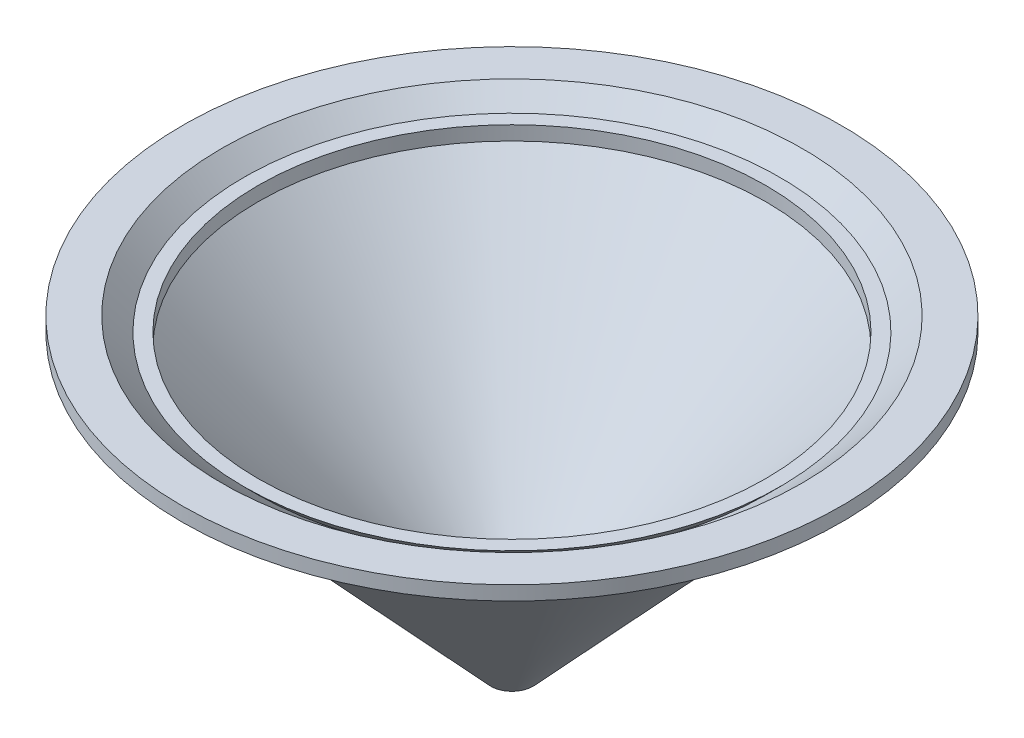
SolidWorks part; units mm, degrees
other "Markup1"
sketch "Sketch4" plane through (66.75, 2, 66.75) normal (0.1882, 0.8238, 0.5348) x (0.9745, -0.0887, -0.2062)
other "Markup2"
sketch "Sketch5" plane through (-66.75, 2, 66.75) normal (-0.3605, 0.8664, 0.3456) x (0.6787, -0.0106, 0.7344)
ref_plane "Front Plane" through (0, 0, 0) normal (0, 0, 1) x (1, 0, 0)
ref_plane "Top Plane" through (0, 0, 0) normal (0, 1, 0) x (1, 0, 0)
ref_plane "Right Plane" through (0, 0, 0) normal (1, 0, 0) x (0, 0, -1)
sketch "Sketch1" plane through (0, 0, 0) normal (0, 1, 0) x (1, 0, 0)
  circle A0 centre (0, 0) radius 46.7275
  dimension "D1" = 93.455
sketch "Sketch2" plane through (0, 0, 0) normal (0, 0, 1) x (1, 0, 0)
  line L0 (0, 0) -> (0, -42)
  line L1 (-42, 0) -> (-3, -42)
  line L2 (46.7275, 0) -> (-46.7275, 0) construction
  line L3 (0, -42) -> (-3, -42)
  line L4 (0, 0) -> (-42, 0)
  line L5 (-3, -42) -> (0, -45) construction
  line L6 (0, -45) -> (0, -42) construction
  dimension "D1" = 42
  dimension "D2" = 42
  dimension "D3" = 3
  dimension "D4" = 3
revolve "Revolve1" add sketch "Sketch2" angle 360 about L0
extrude "Boss-Extrude2" add sketch "Sketch1" along normal blind 2 contours A0
shell "Shell1" thickness 2 removed face at (-3, -42, 0) removed face at (0, 2, 46.7275)
sketch "Sketch3" plane through (0, 0, 0) normal (1, 0, 0) x (0, 0, -1)
  line L0 (-38, 0) -> (-36, 0)
  line L1 (-46.7275, 0) -> (46.7275, 0) construction
  line L2 (-36, 0) -> (-36, -2)
  line L3 (-36, -2) -> (-38, 0)
  line L4 (0, 0) -> (0, -11.1818) construction
  dimension "D1" = 2
  dimension "D2" = 2
  dimension "D3" = 38
revolve "Revolve2" add sketch "Sketch3" angle 360 about L4
